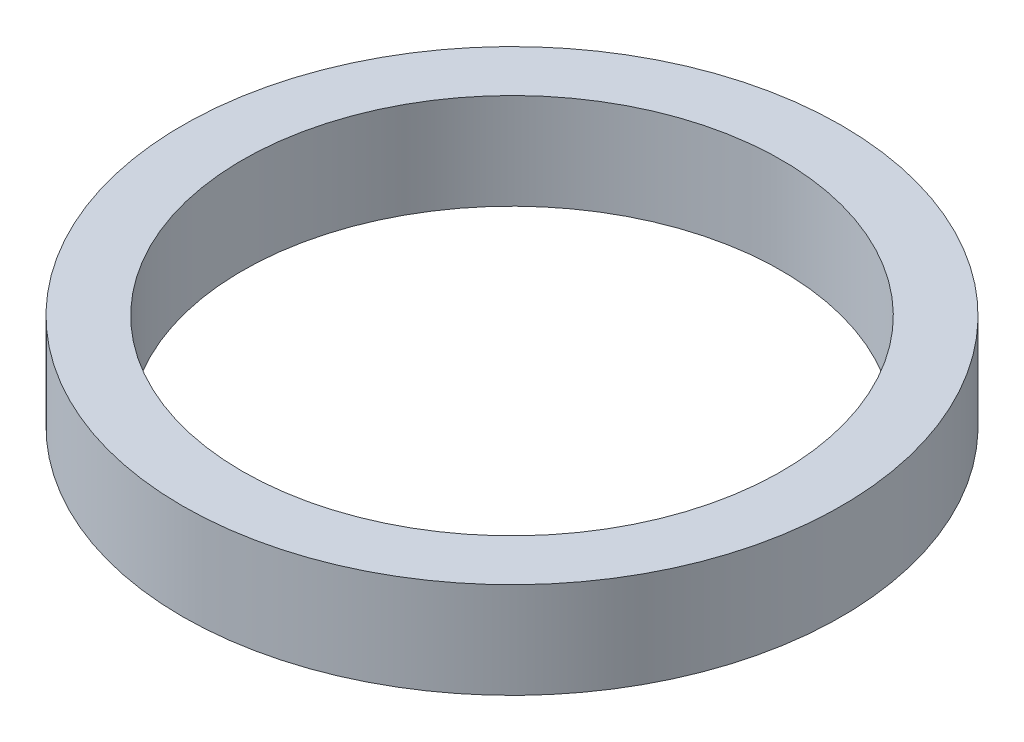
SolidWorks part; units mm, degrees
ref_plane "Front Plane" through (0, 0, 0) normal (0, 0, 1) x (1, 0, 0)
ref_plane "Top Plane" through (0, 0, 0) normal (0, 1, 0) x (1, 0, 0)
ref_plane "Right Plane" through (0, 0, 0) normal (1, 0, 0) x (0, 0, -1)
sketch "Sketch1" plane through (0, 0, 0) normal (0, 1, 0) x (1, 0, 0)
  circle A0 centre (0, 0) radius 55
  dimension "FLANGE_OD" = 110
extrude "Boss-Extrude1" add sketch "Sketch1" along normal blind 16
sketch "Sketch2" plane through (0, 0, 0) normal (0, 1, 0) x (1, 0, 0)
  circle A0 centre (0, 0) radius 45
  dimension "BORE_D" = 90
extrude "Cut-Extrude1" cut sketch "Sketch2" along normal through all
sketch "Sketch3" plane through (0, 16, 0) normal (0, 1, 0) x (1, 0, 0)
  circle A0 centre (0, 0) radius 23.979 construction
  circle A1 centre (-23.979, 0) radius 1.7241
  dimension "BOLT_D" = 3.4481
  dimension "BOLT_PCD" = 47.9581
extrude "Cut-Extrude2" cut sketch "Sketch3" against normal blind 11.1344 rebuild error yes
pattern_circular "CirPattern1" count 4 over 360 rebuild error yes
